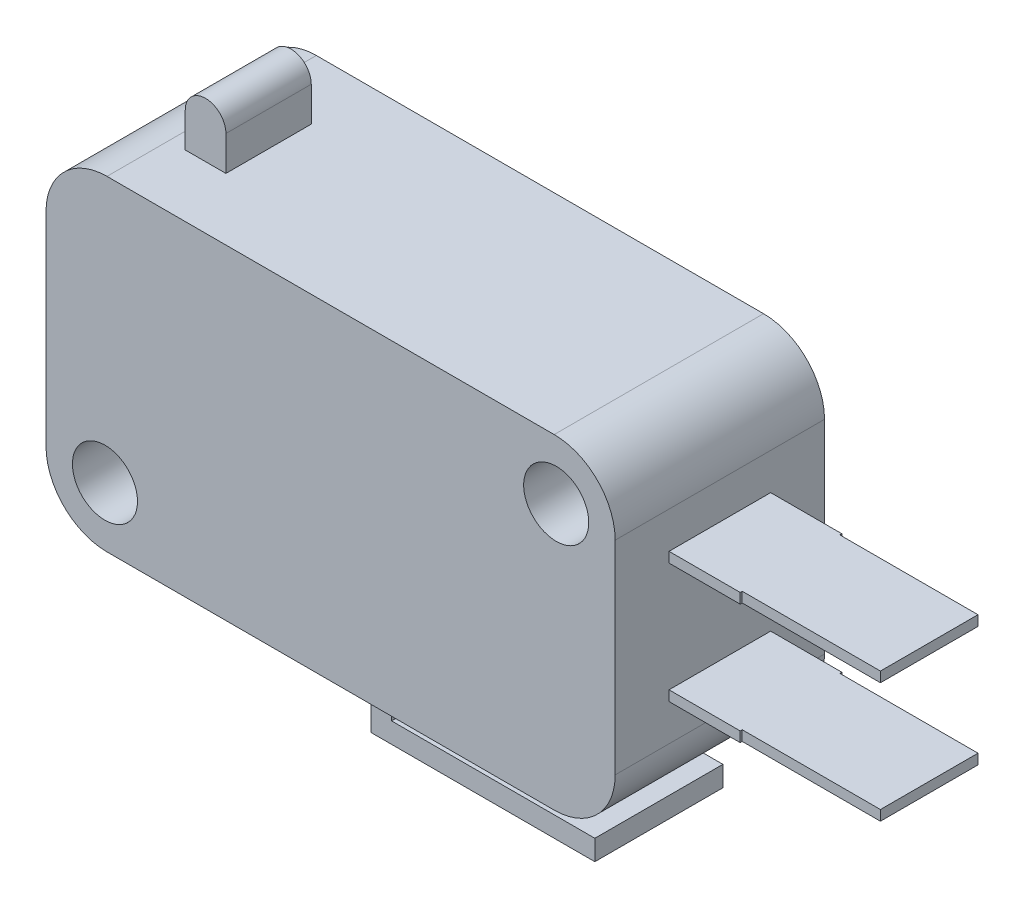
SolidWorks part; units mm, degrees
ref_plane "前视基准面" through (0, 0, 0) normal (0, 0, 1) x (1, 0, 0)
ref_plane "上视基准面" through (0, 0, 0) normal (0, 1, 0) x (1, 0, 0)
ref_plane "右视基准面" through (0, 0, 0) normal (1, 0, 0) x (0, 0, -1)
other "Configuration Table"
sketch "草图1" plane through (0, 0, 0) normal (0, 1, 0) x (1, 0, 0)
  line L1 (0, 0) -> (28, 0)
  line L2 (0, 0) -> (0, 10.3)
  line L3 (0, 10.3) -> (28, 10.3)
  line L4 (28, 0) -> (28, 10.3)
  dimension "D1" = 10.3
  dimension "D2" = 28
extrude "凸台-拉伸1" add sketch "草图1" along normal blind 16
sketch "草图2" plane through (0, 0, 0) normal (0, 0, 1) x (1, 0, 0)
  line L0 (0, 0) -> (28, 0) construction
  line L1 (0, 16) -> (28, 16) construction
  line L2 (0, 16) -> (0, 0) construction
  circle A0 centre (2.9, 2.9) radius 1.6
  circle A1 centre (25.1, 13.1) radius 1.6
  dimension "D1" = 2.9
  dimension "D2" = 2.9
  dimension "D3" = 22.2
  dimension "D4" = 2.9
  dimension "D5" = 3.2
  dimension "D6" = 3.2
extrude "切除-拉伸1" cut sketch "草图2" against normal blind 16
fillet "圆角1" radius 3 4 edges at (28, 0, -5.15) (0, 0, -5.15) (28, 16, -5.15) (0, 16, -5.15)
sketch "草图3" plane through (0, 0, 0) normal (0, 0, 1) x (1, 0, 0)
  line L0 (3.8, 16) -> (3.8, 17.7)
  line L1 (3, 16) -> (25, 16) construction
  line L2 (5.8, 17.7) -> (5.8, 16)
  line L3 (5.8, 16) -> (3.8, 16)
  arc A0 (5.8, 17.7) -> (3.8, 17.7) centre (4.8, 17.7) ccw
  circle A1 centre (25.1, 13.1) radius 1.6 construction
  point P5 (4.9226, 17.7375)
  point P8 (3.8629, 17.2696)
  dimension "D2" = 1
  dimension "D3" = 1.7
  dimension "D1" = 20.3
extrude "凸台-拉伸2" add sketch "草图3" against normal blind 4.2 from offset 3.05 offset against normal yes
sketch "草图4" plane through (28, 0, 0) normal (1, 0, 0) x (0, 0, -1)
  line L0 (5.15, 16) -> (5.15, 0) construction
  line L1 (2.65, 11.2) -> (7.65, 11.2)
  line L2 (2.65, 11.2) -> (2.65, 10.7)
  line L3 (2.65, 10.7) -> (7.65, 10.7)
  line L4 (7.65, 11.2) -> (7.65, 10.7)
  line L5 (2.65, 5.3) -> (7.65, 5.3)
  line L6 (2.65, 5.3) -> (2.65, 4.8)
  line L7 (2.65, 4.8) -> (7.65, 4.8)
  line L8 (7.65, 5.3) -> (7.65, 4.8)
  line L9 (7.25, 16) -> (3.05, 16) construction
  line L10 (10.3, 0) -> (0, 0) construction
  line L11 (0, 8) -> (10.3, 8) construction
  line L12 (0, 13) -> (0, 3) construction
  line L13 (10.3, 13) -> (10.3, 3) construction
  point P14 (0, 0)
  dimension "D1" = 0.5
  dimension "D2" = 0.5
  dimension "D3" = 6.4
  dimension "D4" = 5
extrude "凸台-拉伸3" add sketch "草图4" along normal blind 10.3
sketch "草图5" plane through (0, 11.2, 0) normal (0, 1, 0) x (1, 0, 0)
  line L0 (38.3, 7.65) -> (28, 7.65) construction
  line L1 (31.5, 7.65) -> (38.3, 7.65)
  line L2 (31.5, 7.65) -> (31.5, 7.55)
  line L3 (31.5, 7.55) -> (38.3, 7.55)
  line L4 (38.3, 7.65) -> (38.3, 7.55)
  line L5 (38.3, 7.65) -> (38.3, 2.65) construction
  line L6 (38.3, 5.15) -> (28, 5.15) construction
  line L7 (38.3, 2.65) -> (31.5, 2.65)
  line L8 (38.3, 2.65) -> (38.3, 2.75)
  line L9 (38.3, 2.75) -> (31.5, 2.75)
  line L10 (31.5, 2.65) -> (31.5, 2.75)
  line L11 (28, 7.65) -> (28, 2.65) construction
  dimension "D1" = 0.1
  dimension "D2" = 0.1
  dimension "D3" = 6.8
  dimension "D4" = 6.8
extrude "切除-拉伸2" cut sketch "草图5" against normal through all
sketch "草图6" plane through (0, 0, 0) normal (0, 0, 1) x (1, 0, 0)
  line L0 (14, 0) -> (14, -3.2)
  line L1 (3, 0) -> (25, 0) construction
  line L2 (14, -3.2) -> (25, -3.2)
  line L3 (25, -3.2) -> (25, -2.2)
  line L4 (25, -2.2) -> (15, -2.2)
  line L5 (15, -2.2) -> (15, 0)
  line L6 (15, 0) -> (14, 0)
  line L7 (28, 13) -> (28, 3) construction
  point P4 (25.3428, -2.0154)
  dimension "D1" = 3.2
  dimension "D2" = 1
  dimension "D3" = 1
  dimension "D4" = 13
  dimension "D5" = 11
extrude "凸台-拉伸4" add sketch "草图6" against normal blind 6.3 from offset 2 offset against normal yes
ref_plane "基准面1" through (0, 0, -5.15) normal (0, 0, 1) x (1, 0, 0)
sketch "草图7" plane through (0, 0, -5.15) normal (0, 0, 1) x (1, 0, 0)
  line L0 (2.3, 18.75) -> (16.3, 18.75)
  line L1 (16.3, 18.75) -> (16.3, 16)
  line L2 (3, 16) -> (25, 16) construction
  line L3 (16.3, 16) -> (17.3, 16)
  line L4 (17.3, 16) -> (17.3, 19.75)
  line L5 (17.3, 19.75) -> (2.3, 19.75)
  line L6 (2.3, 19.75) -> (2.3, 18.75)
  arc A1 (5.8, 17.7) -> (3.8, 17.7) centre (4.8, 17.7) ccw construction
  dimension "D1" = 12.5
  dimension "D2" = 1
  dimension "D3" = 1
  dimension "D4" = 2.5
  dimension "D5" = 2.75
extrude "凸台-拉伸7" [suppressed] add sketch "草图7" along normal blind 2 and the other way blind 2
sketch "草图8" [suppressed] plane through (0, 19.75, 0) normal (0, 1, 0) x (1, 0, 0)
  line L0 (4.8, 7.15) -> (4.8, 3.15) construction
  line L1 (2.3, 7.15) -> (7.3, 7.15)
  line L2 (2.3, 7.15) -> (2.3, 6.15)
  line L3 (2.3, 6.15) -> (7.3, 6.15)
  line L4 (7.3, 7.15) -> (7.3, 6.15)
  line L5 (2.3, 3.15) -> (7.3, 3.15)
  line L6 (2.3, 3.15) -> (2.3, 4.15)
  line L7 (2.3, 4.15) -> (7.3, 4.15)
  line L8 (7.3, 3.15) -> (7.3, 4.15)
  line L9 (17.3, 7.15) -> (17.3, 3.15) construction
  dimension "D1" = 1
  dimension "D2" = 1
  dimension "D3" = 12.5
extrude "凸台-拉伸8" [suppressed] add sketch "草图8" along normal blind 4
fillet "圆角2" [suppressed] radius 2.5
sketch "草图9" [suppressed] plane through (0, 0, -4.15) normal (0, 0, -1) x (-1, 0, 0)
  circle A0 centre (-4.8, 21.25) radius 2.5
  dimension "D1" = 5
extrude "凸台-拉伸9" [suppressed] add sketch "草图9" along normal up to surface (2 mm away)
